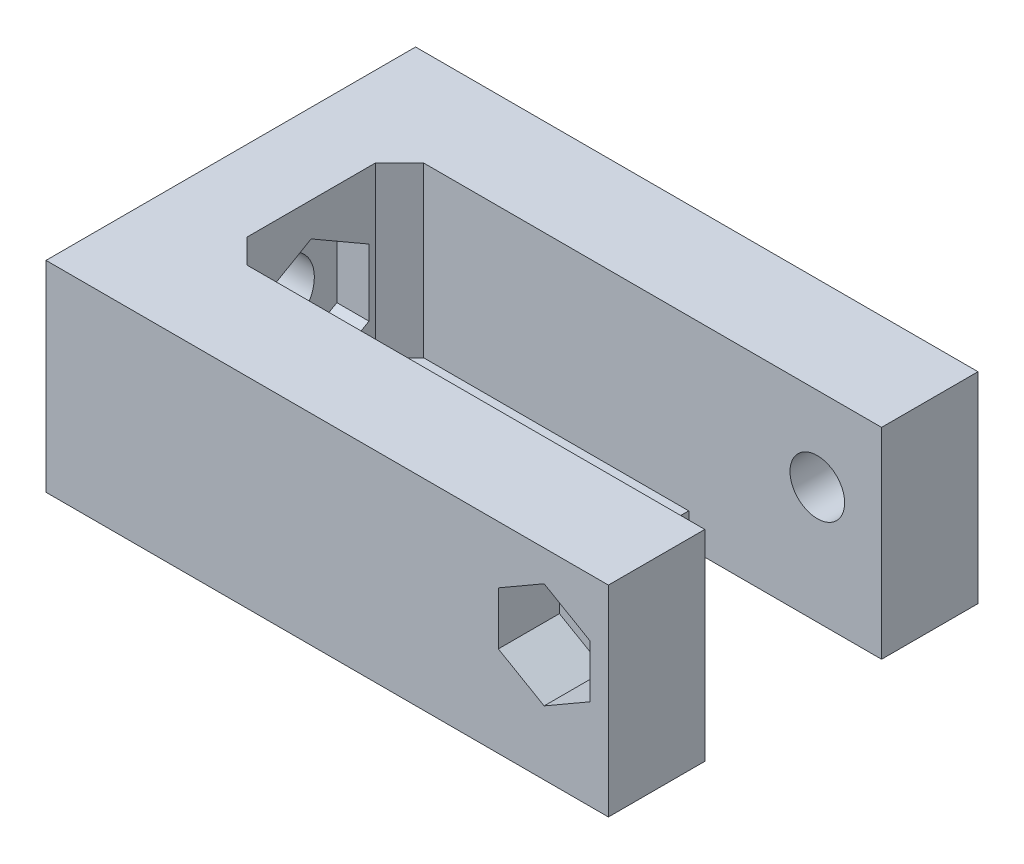
SolidWorks part; units mm, degrees
ref_plane "Front Plane" through (0, 0, 0) normal (0, 0, 1) x (1, 0, 0)
ref_plane "Top Plane" through (0, 0, 0) normal (0, 1, 0) x (1, 0, 0)
ref_plane "Right Plane" through (0, 0, 0) normal (1, 0, 0) x (0, 0, -1)
sketch "Sketch1" plane through (0, 0, 0) normal (1, 0, 0) x (0, 0, -1)
  line L1 (0, 0) -> (23, 0)
  line L2 (0, 0) -> (0, 12.5)
  line L3 (0, 12.5) -> (23, 12.5)
  line L4 (23, 0) -> (23, 12.5)
  dimension "D1" = 23
  dimension "D2" = 12.5
extrude "Boss-Extrude1" add sketch "Sketch1" along normal blind 35
sketch "Sketch2" plane through (35, 0, 0) normal (1, 0, 0) x (0, 0, -1)
  line L0 (11.5, 12.5) -> (11.5, 0) construction
  line L1 (6, 12.5) -> (17, 12.5)
  line L2 (6, 12.5) -> (6, 0)
  line L3 (6, 0) -> (17, 0)
  line L4 (17, 12.5) -> (17, 0)
  line L5 (0, 0) -> (23, 0) construction
  line L8 (23, 12.5) -> (0, 12.5) construction
  line L9 (11.5, 12.5) -> (11.5, 0) construction
  dimension "D1" = 11
extrude "Cut-Extrude1" cut sketch "Sketch2" against normal offset from surface (30 mm away) 5 up to face at (0, 6.25, -11.5)
sketch "Sketch3" plane through (0, 0, -23) normal (0, 0, -1) x (-1, 0, 0)
  line L1 (-35, 0) -> (-35, 12.5) construction
  line L2 (-35, 0) -> (0, 0) construction
  circle A0 centre (-31, 7.28) radius 1.7
  dimension "D3" = 3.4
  dimension "D1" = 7.28
  dimension "D2" = 4
extrude "Cut-Extrude2" cut sketch "Sketch3" against normal through all both and the other way through all
sketch "Sketch4" plane through (0, 0, 0) normal (-1, 0, 0) x (0, 0, 1)
  line L0 (-11.5, 12.5) -> (-11.5, 0) construction
  line L3 (-17, 12.5) -> (-6, 12.5) construction
  line L6 (-6, 0) -> (-17, 0) construction
  circle A0 centre (-11.5, 6.25) radius 2.2
  point P6 (-13.473, 5)
  dimension "D1" = 4.4
  dimension "D2" = 6.25
extrude "Cut-Extrude3" cut sketch "Sketch4" against normal blind 10
sketch "Sketch5" plane through (5, 0, 0) normal (1, 0, 0) x (0, 0, -1)
  line L1 (7.9, 8.3285) -> (7.9, 4.1715)
  line L2 (7.9, 4.1715) -> (11.5, 2.0931)
  line L3 (11.5, 2.0931) -> (15.1, 4.1715)
  line L4 (15.1, 4.1715) -> (15.1, 8.3285)
  line L5 (15.1, 8.3285) -> (11.5, 10.4069)
  line L6 (11.5, 10.4069) -> (7.9, 8.3285)
  circle A0 centre (11.5, 6.25) radius 3.6 construction
  dimension "D1" = 7.2
extrude "Cut-Extrude4" cut sketch "Sketch5" against normal blind 2
sketch "Sketch6" plane through (0, 0, -23) normal (0, 0, -1) x (-1, 0, 0)
  circle A0 centre (-31, 7.28) radius 3.25
  dimension "D1" = 6.5
extrude "Cut-Extrude5" cut sketch "Sketch6" against normal blind 2.5
sketch "Sketch7" plane through (0, 0, 0) normal (0, 0, 1) x (1, 0, 0)
  line L1 (28.15, 8.9254) -> (28.15, 5.6346)
  line L2 (28.15, 5.6346) -> (31, 3.9891)
  line L3 (31, 3.9891) -> (33.85, 5.6346)
  line L4 (33.85, 5.6346) -> (33.85, 8.9254)
  line L5 (33.85, 8.9254) -> (31, 10.5709)
  line L6 (31, 10.5709) -> (28.15, 8.9254)
  circle A0 centre (31, 7.28) radius 2.85 construction
  dimension "D1" = 5.7
extrude "Cut-Extrude6" cut sketch "Sketch7" against normal blind 3.8
sketch "Sketch8" plane through (0, 0, -6) normal (0, 0, -1) x (-1, 0, 0)
  line L0 (-5, 0) -> (-35, 0) construction
  line L1 (-23, 0) -> (-5, 0)
  line L2 (-23, 0) -> (-23, 2)
  line L3 (-23, 2) -> (-5, 2)
  line L4 (-5, 0) -> (-5, 2)
  dimension "D1" = 2
  dimension "D2" = 18
extrude "Boss-Extrude2" add sketch "Sketch8" along normal up to surface (11 mm away) up to face at (29.3, 7.28, -17)
chamfer "Chamfer2" distance 1.5 angle 45 2 edges at (5, 7.25, -6) (5, 7.25, -17)
